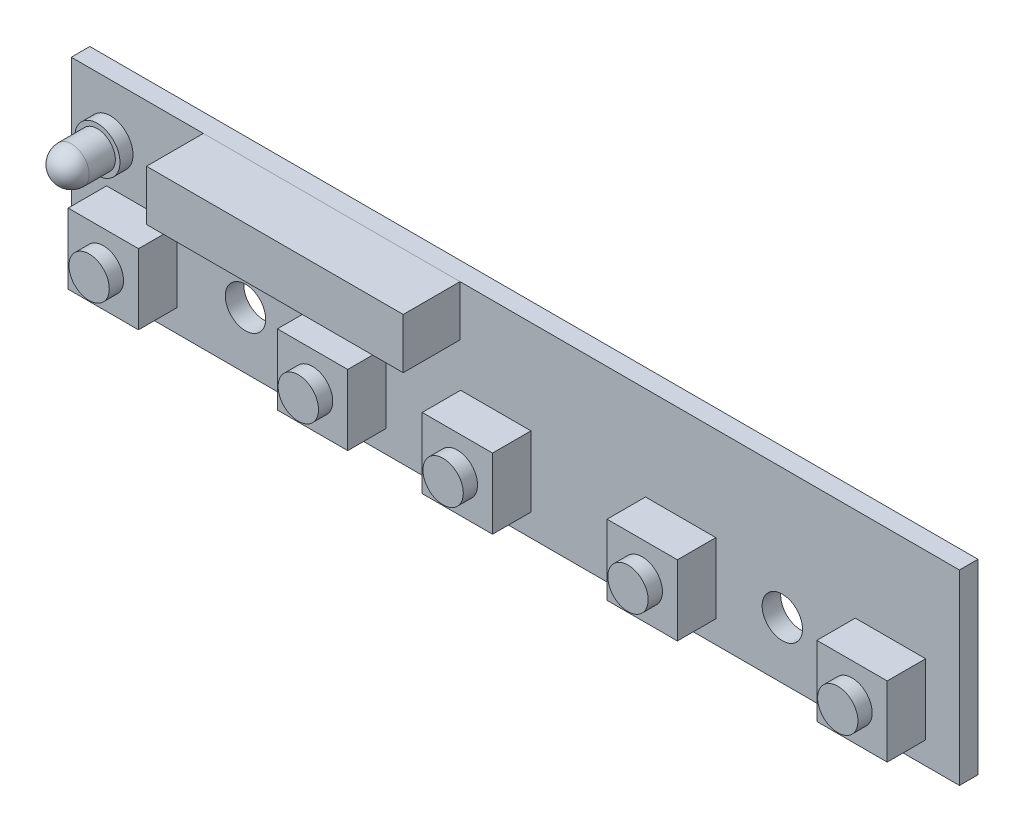
SolidWorks part; units mm, degrees
ref_plane "Front Plane" through (0, 0, 0) normal (0, 0, 1) x (1, 0, 0)
ref_plane "Top Plane" through (0, 0, 0) normal (0, 1, 0) x (1, 0, 0)
ref_plane "Right Plane" through (0, 0, 0) normal (1, 0, 0) x (0, 0, -1)
sketch "Sketch2" plane through (0, 0, 0) normal (0, 0, 1) x (1, 0, 0)
  line L0 (-38.0111, -3.1115) -> (38.0111, -3.1115) construction
  line L1 (-38.0111, -7.9883) -> (38.0111, -7.9883)
  line L2 (-38.0111, -7.9883) -> (-38.0111, 7.9883)
  line L3 (-38.0111, 7.9883) -> (38.0111, 7.9883)
  line L4 (38.0111, -7.9883) -> (38.0111, 7.9883)
  line L5 (-38.0111, -7.9883) -> (38.0111, 7.9883) construction
  line L6 (-38.0111, 7.9883) -> (38.0111, -7.9883) construction
  circle A0 centre (-23.1013, -3.1115) radius 1.7272
  circle A1 centre (22.8473, -3.1115) radius 1.7272
  point P0 (0, 0)
  point P12 (-24.8285, -3.1115)
  point P13 (-23.1013, -4.8387)
  point P14 (24.5745, -3.1115)
  dimension "D5" = 3.4544
  dimension "D1" = 76.0222
  dimension "D2" = 15.9766
  dimension "D3" = 13.1826
  dimension "D4" = 3.1496
  dimension "D6" = 13.4366
extrude "Boss-Extrude1" add sketch "Sketch2" against normal blind 1.5875
sketch "Sketch3" plane through (0, 0, 0) normal (0, 0, 1) x (1, 0, 0)
  line L0 (-38.0111, -3.048) -> (38.0111, -3.048) construction
  line L1 (-34.9885, -6.0579) -> (-28.9687, -6.0579)
  line L2 (-34.9885, -6.0579) -> (-34.9885, -0.0381)
  line L3 (-34.9885, -0.0381) -> (-28.9687, -0.0381)
  line L4 (-28.9687, -6.0579) -> (-28.9687, -0.0381)
  line L5 (-34.9885, -6.0579) -> (-28.9687, -0.0381) construction
  line L6 (-34.9885, -0.0381) -> (-28.9687, -6.0579) construction
  line L7 (-17.0815, -6.0579) -> (-11.0617, -6.0579)
  line L8 (-17.0815, -6.0579) -> (-17.0815, -0.0381)
  line L9 (-17.0815, -0.0381) -> (-11.0617, -0.0381)
  line L10 (-11.0617, -6.0579) -> (-11.0617, -0.0381)
  line L11 (-17.0815, -6.0579) -> (-11.0617, -0.0381) construction
  line L12 (-17.0815, -0.0381) -> (-11.0617, -6.0579) construction
  line L13 (-4.6863, -6.0579) -> (1.3335, -6.0579)
  line L14 (-4.6863, -6.0579) -> (-4.6863, -0.0381)
  line L15 (-4.6863, -0.0381) -> (1.3335, -0.0381)
  line L16 (1.3335, -6.0579) -> (1.3335, -0.0381)
  line L17 (-4.6863, -6.0579) -> (1.3335, -0.0381) construction
  line L18 (-4.6863, -0.0381) -> (1.3335, -6.0579) construction
  line L19 (11.1379, -0.0381) -> (17.1577, -0.0381)
  line L20 (11.1379, -0.0381) -> (11.1379, -6.0579)
  line L21 (11.1379, -6.0579) -> (17.1577, -6.0579)
  line L22 (17.1577, -0.0381) -> (17.1577, -6.0579)
  line L23 (11.1379, -0.0381) -> (17.1577, -6.0579) construction
  line L24 (11.1379, -6.0579) -> (17.1577, -0.0381) construction
  line L25 (29.0957, -0.0381) -> (35.1155, -0.0381)
  line L26 (29.0957, -0.0381) -> (29.0957, -6.0579)
  line L27 (29.0957, -6.0579) -> (35.1155, -6.0579)
  line L28 (35.1155, -0.0381) -> (35.1155, -6.0579)
  line L29 (29.0957, -0.0381) -> (35.1155, -6.0579) construction
  line L30 (29.0957, -6.0579) -> (35.1155, -0.0381) construction
  line L31 (-38.0111, 7.9883) -> (-38.0111, -7.9883) construction
  line L32 (38.0111, -7.9883) -> (38.0111, 7.9883) construction
  line L33 (-38.0111, -7.9883) -> (38.0111, -7.9883) construction
  point P0 (-31.9786, -3.048)
  point P5 (-14.0716, -3.048)
  point P10 (-1.6764, -3.048)
  point P15 (14.1478, -3.048)
  point P20 (32.1056, -3.048)
  dimension "D1" = 6.0198
  dimension "D2" = 3.0226
  dimension "D3" = 23.9268
  dimension "D4" = 18.415
  dimension "D5" = 21.844
  dimension "D6" = 23.9776
  dimension "D7" = 7.9502
extrude "Boss-Extrude2" add sketch "Sketch3" along normal blind 3.2893 separate body
sketch "Sketch4" plane through (0, 0, 3.2893) normal (0, 0, 1) x (1, 0, 0)
  line L0 (-34.9885, -6.0579) -> (-28.9687, -0.0381) construction
  line L1 (-17.0815, -6.0579) -> (-11.0617, -0.0381) construction
  line L2 (-4.6863, -6.0579) -> (1.3335, -0.0381) construction
  line L3 (11.1379, -6.0579) -> (17.1577, -0.0381) construction
  line L4 (29.0957, -6.0579) -> (35.1155, -0.0381) construction
  circle A0 centre (-31.9786, -3.048) radius 1.7272
  circle A1 centre (-14.0716, -3.048) radius 1.7272
  circle A2 centre (-1.6764, -3.048) radius 1.7272
  circle A3 centre (14.1478, -3.048) radius 1.7272
  circle A4 centre (32.1056, -3.048) radius 1.7272
  dimension "D1" = 3.4544
extrude "Boss-Extrude3" add sketch "Sketch4" along normal blind 1.2192
sketch "Sketch5" plane through (0, 0, 0) normal (0, 0, 1) x (1, 0, 0)
  line L0 (38.0111, 7.9883) -> (-38.0111, 7.9883) construction
  line L1 (-26.7081, 7.9883) -> (-4.7371, 7.9883)
  line L2 (-26.7081, 7.9883) -> (-26.7081, 3.6703)
  line L3 (-26.7081, 3.6703) -> (-4.7371, 3.6703)
  line L4 (-4.7371, 7.9883) -> (-4.7371, 3.6703)
  line L5 (-38.0111, 7.9883) -> (-38.0111, -7.9883) construction
  dimension "D1" = 11.303
  dimension "D2" = 21.971
  dimension "D3" = 4.318
extrude "Boss-Extrude4" add sketch "Sketch5" along normal blind 4.8641 separate body
sketch "Sketch6" plane through (0, 0, 0) normal (0, 0, 1) x (1, 0, 0)
  line L1 (-38.0111, 7.9883) -> (-38.0111, -7.9883) construction
  line L2 (38.0111, 7.9883) -> (-38.0111, 7.9883) construction
  circle A0 centre (-33.7693, 4.2799) radius 1.5367
  dimension "D3" = 3.0734
  dimension "D1" = 4.2418
  dimension "D2" = 3.7084
extrude "Boss-Extrude5" add sketch "Sketch6" along normal blind 3.3528 from offset 0.889 separate body
dome "Dome1" faces to dome 1 distance 1.5367 reverse direction no elliptical dome no face at (-32.2326, 4.2799, 4.2418) parameters "D1"=1.5367
sketch "Sketch7" plane through (0, 0, 0.889) normal (0, 0, -1) x (-1, 0, 0)
  circle A0 centre (33.7693, 4.2799) radius 1.9304
  dimension "D1" = 3.8608
extrude "Boss-Extrude6" add sketch "Sketch7" against normal blind 1.1176
